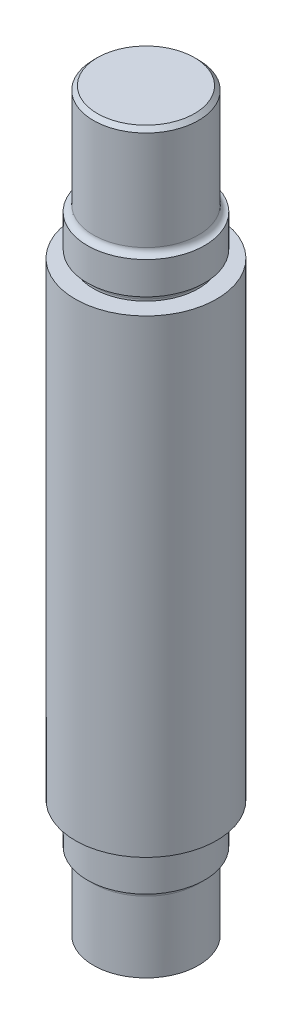
SolidWorks part; units mm, degrees
ref_plane "Front Plane" through (0, 0, 0) normal (0, 0, 1) x (1, 0, 0)
ref_plane "Top Plane" through (0, 0, 0) normal (0, 1, 0) x (1, 0, 0)
ref_plane "Right Plane" through (0, 0, 0) normal (1, 0, 0) x (0, 0, -1)
sketch "Sketch1" plane through (0, 0, 0) normal (0, 0, 1) x (1, 0, 0)
  line L1 (-22.55, 98.7263) -> (-0.15, 98.7263)
  line L2 (-22.55, 98.7263) -> (-22.55, 52.1263)
  line L5 (-25.15, 52.1263) -> (-22.55, 52.1263)
  line L14 (-0.15, 98.7263) -> (-0.15, -215.0737)
  line L16 (-25.15, -182.2737) -> (-25.15, -168.4737)
  line L17 (-25.15, -182.2737) -> (-22.55, -182.2737)
  line L18 (-22.55, -215.0737) -> (-22.55, -182.2737)
  line L19 (-22.55, -215.0737) -> (-0.15, -215.0737)
  line L20 (-25.15, 52.1263) -> (-25.15, 38.3263)
  line L21 (-25.15, 38.3263) -> (-22.55, 38.3263)
  line L22 (-22.55, 38.3263) -> (-22.55, 34.9263)
  line L23 (-22.55, 34.9263) -> (-30.3, 34.9263)
  line L24 (-25.15, -168.4737) -> (-22.55, -168.4737)
  line L25 (-22.55, -168.4737) -> (-22.55, -165.0737)
  line L26 (-22.55, -165.0737) -> (-30.3, -165.0737)
  line L27 (-30.3, -165.0737) -> (-30.3, 34.9263)
revolve "Revolve3" add sketch "Sketch1" angle 360 about L14
chamfer "Chamfer1" distance 1.7 angle 45 1 edges at (-22.55, 98.7263, 0)
fillet "Fillet4" radius 2.6 1 edges at (-22.55, 52.1263, 0)
fillet "Fillet7" radius 2.6 1 edges at (-22.55, 38.3263, 0)
fillet "Fillet8" radius 2.6 1 edges at (-22.55, -182.2737, 0)
fillet "Fillet9" radius 2.6 1 edges at (-22.55, -168.4737, 0)
